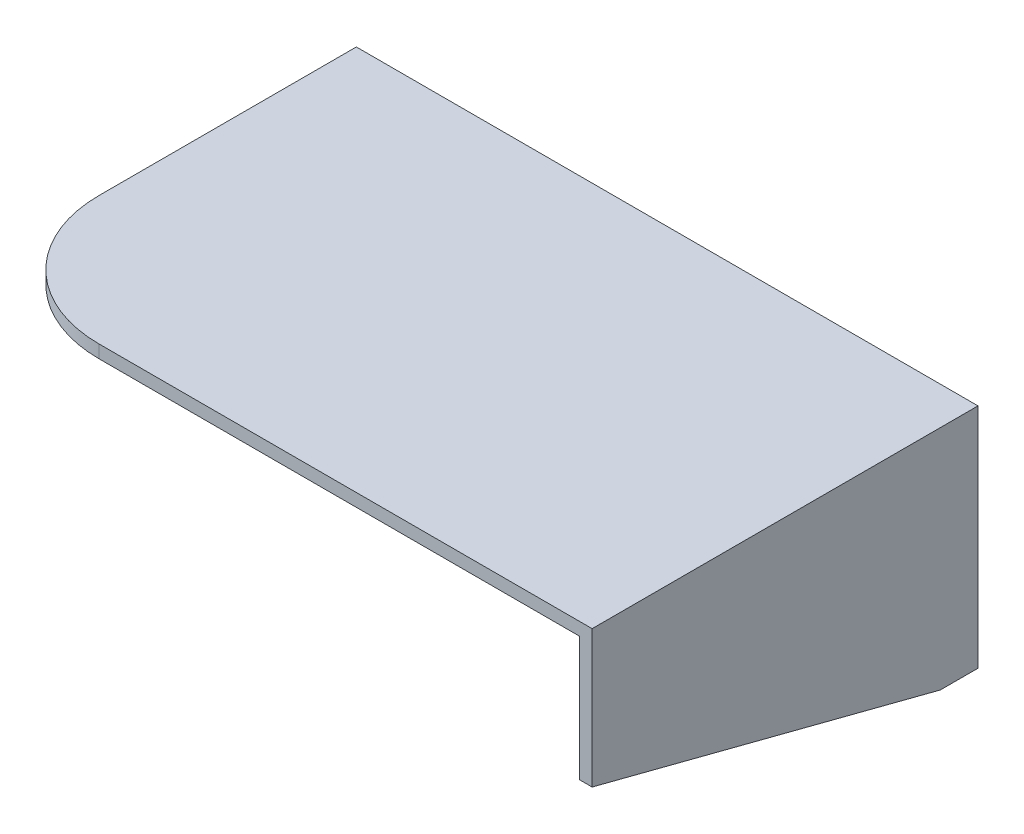
SolidWorks part; units mm, degrees
ref_plane "Front Plane" through (0, 0, 0) normal (0, 0, 1) x (1, 0, 0)
ref_plane "Top Plane" through (0, 0, 0) normal (0, 1, 0) x (1, 0, 0)
ref_plane "Right Plane" through (0, 0, 0) normal (1, 0, 0) x (0, 0, -1)
sketch "Sketch2" plane through (0, 0, 0) normal (0, 0, 1) x (1, 0, 0)
  line L0 (0, 4.05) -> (2.5, 4.05)
  line L1 (0, -4.05) -> (10.5, -4.05)
  line L2 (2.5, 4.05) -> (2.5, 30.95)
  line L3 (2.5, 30.95) -> (-49.5, 30.95)
  line L4 (-49.5, 30.95) -> (-49.5, 33.95)
  line L5 (-49.5, 33.95) -> (10.5, 33.95)
  line L6 (10.5, 33.95) -> (10.5, -4.05)
  line L7 (2.5, 30.95) -> (10.5, 30.95)
  line L8 (10.5, 33.95) -> (95.5, 33.95)
  line L9 (95.5, 33.95) -> (95.5, -19.05)
  line L10 (95.5, -19.05) -> (10.5, -19.05)
  line L11 (10.5, -19.05) -> (10.5, -4.05)
  line L12 (10.5, 30.95) -> (92.5, 30.95)
  line L13 (30.5, 33.95) -> (30.5, 30.95)
  line L14 (92.5, 30.95) -> (92.5, -19.05)
  point P4 (0, 0)
  line B0 (0, -7.95) -> (-2.04, -7.95)
  line B1 (-6.1524, -4.048) -> (-6.1524, 4.048)
  line B2 (-2.04, 7.95) -> (0, 7.95)
  line B3 (0, 7.95) -> (0, -7.95)
  line B4 (-2.04, -7.95) -> (-6.1524, -4.048)
  line B5 (-6.1524, 4.048) -> (-2.04, 7.95)
  line B6 (0, -4.05) -> (0, 4.05) construction
  dimension "D1" = 10.5
  dimension "D2" = 8
  dimension "D3" = 3
  dimension "D4" = 60
  dimension "D5" = 35
  dimension "D6" = 85
  dimension "D7" = 50
  dimension "D8" = 20
  dimension "D9" = 3
sketch_block_instance "Extrusion Profile-1"
sketch_block "Block1" parameters "D1"=8.44, "D2"=2.6, "D3"=6, "D4"=16.7, "D6"=5.6686, "D7"=2.0404, "D8"=8.0963, "D9"=15.9, "D5"=2.4157
extrude "Boss-Extrude1" add sketch "Sketch2" along normal blind 6 contours L0 B3 L1 L6 L7 L2 | B2 B5 B1 B4 B0 B3 region at (-2.7416, 0, 0) region at (6.1459, 12.5429, 0)
extrude "Boss-Extrude2" add sketch "Sketch2<3>" along normal blind 90 contours L3 L7 L6 L5 L4 | L13 L8 L6 | L12 L14 L10 L9 L8 L13 region at (-19.5, 32.45, 0) region at (20.5, 32.45, 0) region at (31.3387, 32.45, 0)
sketch "Sketch2<3>" plane through (0, 0, 0) normal (0, 0, 1) x (1, 0, 0) same geometry as "Sketch2"
extrude "Boss-Extrude3" add sketch "Sketch2<4>" along normal blind 3 contours L6 L11 L10 L9 | L8 L13 L9 region at (51.5, 5.95, 0) region at (31.3387, 32.45, 0)
sketch "Sketch2<4>" plane through (0, 0, 0) normal (0, 0, 1) x (1, 0, 0) same geometry as "Sketch2"
fillet "Fillet1" radius 3 1 edges at (10.5, 13.45, 3)
fillet "Fillet2" radius 3 1 edges at (10.5, 13.45, 6)
fillet "Fillet3" radius 30 1 edges at (-49.5, 32.45, 90)
sketch "Sketch3" plane through (0, 0, 0) normal (0, 0, -1) x (-1, 0, 0)
  line L0 (-2.5, 4.05) -> (-2.5, -4.05)
  line L1 (0, -4.05) -> (-10.5, -4.05) construction
  line L18 (49.5, 33.95) -> (-95.5, 33.95)
  line L19 (-95.5, 33.95) -> (-95.5, -19.05)
  line L20 (-95.5, -19.05) -> (-10.5, -19.05)
  line L21 (-10.5, -19.05) -> (-10.5, -4.05)
  line L22 (-10.5, -4.05) -> (0, -4.05)
  line L23 (0, -4.05) -> (0, -7.95)
  line L24 (0, -7.95) -> (2.04, -7.95)
  line L25 (2.04, -7.95) -> (6.1524, -4.048)
  line L26 (6.1524, -4.048) -> (6.1524, 4.048)
  line L27 (6.1524, 4.048) -> (2.04, 7.95)
  line L28 (2.04, 7.95) -> (0, 7.95)
  line L29 (0, 7.95) -> (0, 4.05)
  line L30 (0, 4.05) -> (-2.5, 4.05)
  line L31 (-2.5, 4.05) -> (-2.5, 30.95)
  line L32 (-2.5, 30.95) -> (49.5, 30.95)
  line L33 (49.5, 30.95) -> (49.5, 33.95)
  line L34 (49.5, 33.95) -> (-95.5, 33.95)
  line L35 (-95.5, 33.95) -> (-95.5, -19.05)
  line L36 (-95.5, -19.05) -> (-10.5, -19.05)
  line L37 (-10.5, -19.05) -> (-10.5, -4.05)
  line L38 (-10.5, -4.05) -> (-2.5, -4.05)
  line L47 (-2.5, 4.05) -> (-2.5, 30.95)
  line L48 (-2.5, 30.95) -> (49.5, 30.95)
  line L49 (49.5, 30.95) -> (49.5, 33.95)
  dimension "D1" = 0
sketch "Sketch4" plane through (0, 0, 0) normal (0, 0, -1) x (-1, 0, 0)
  line L0 (6.1524, 1) -> (6.1524, -1)
  line L1 (6.1524, -4.048) -> (6.1524, 4.048) construction
  line L2 (6.1524, -1) -> (2.1524, -1)
  line L3 (2.1524, -1) -> (2.1524, 1)
  line L4 (2.1524, 1) -> (6.1524, 1)
  point P5 (6.1524, 0)
  dimension "D1" = 2
  dimension "D2" = 4
extrude "Cut-Extrude1" cut sketch "Sketch4" against normal through all
sketch "Sketch5" plane through (95.5, 0, 0) normal (1, 0, 0) x (0, 0, -1)
  line L0 (-8.799, -19.05) -> (-90, 1.95)
  line L1 (-90, -19.05) -> (0, -19.05) construction
  line L2 (-90, 33.95) -> (-90, -19.05) construction
  line L3 (-90, 1.95) -> (-90, -19.05)
  line L4 (-90, -19.05) -> (-8.799, -19.05)
  dimension "D1" = 21
  dimension "D2" = 14.5
extrude "Cut-Extrude2" cut sketch "Sketch5" against normal through all
